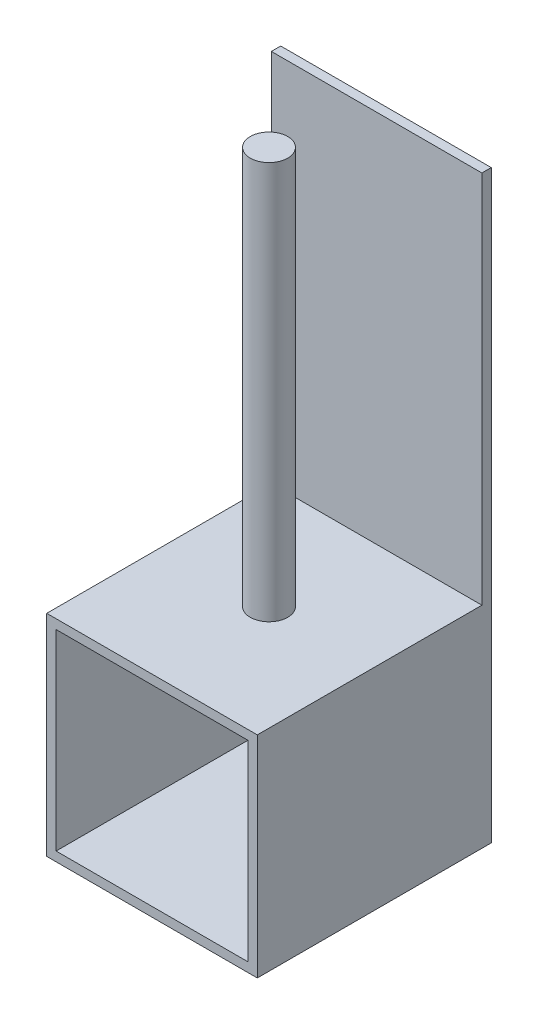
SolidWorks part; units mm, degrees
material "Cast Alloy Steel"
ref_plane "Front Plane" through (0, 0, 0) normal (0, 0, 1) x (1, 0, 0)
ref_plane "Top Plane" through (0, 0, 0) normal (0, 1, 0) x (1, 0, 0)
ref_plane "Right Plane" through (0, 0, 0) normal (1, 0, 0) x (0, 0, -1)
sketch "Sketch1" plane through (0, 0, 0) normal (0, 0, 1) x (1, 0, 0)
  line L0 (2, -2) -> (43, -2)
  line L1 (0, 0) -> (45, 0)
  line L2 (0, 0) -> (0, -45)
  line L3 (0, -45) -> (45, -45)
  line L4 (45, 0) -> (45, -45)
  line L5 (43, -2) -> (43, -43)
  line L6 (2, -43) -> (43, -43)
  line L7 (2, -2) -> (2, -43)
  dimension "D1" = 45
  dimension "D2" = 45
  dimension "D3" = 2
extrude "Boss-Extrude1" add sketch "Sketch1" along normal blind 50
sketch "Sketch2" plane through (0, 0, 0) normal (0, 1, 0) x (1, 0, 0)
  line L1 (0, 0) -> (45, 0)
  line L2 (0, 0) -> (0, -2)
  line L3 (0, -2) -> (45, -2)
  line L4 (45, 0) -> (45, -2)
  dimension "D1" = 45
  dimension "D2" = 2
extrude "Boss-Extrude2" add sketch "Sketch2" along normal blind 80
sketch "Sketch3" plane through (0, 0, 0) normal (0, 1, 0) x (1, 0, 0)
  line L0 (22.5, -4) -> (22.5, -50) construction
  line L1 (0, -4) -> (45, -4) construction
  line L2 (45, -50) -> (0, -50) construction
  circle A0 centre (22.5, -25) radius 4
  dimension "D1" = 8
  dimension "D2" = 25
extrude "Boss-Extrude3" add sketch "Sketch3" along normal blind 85
